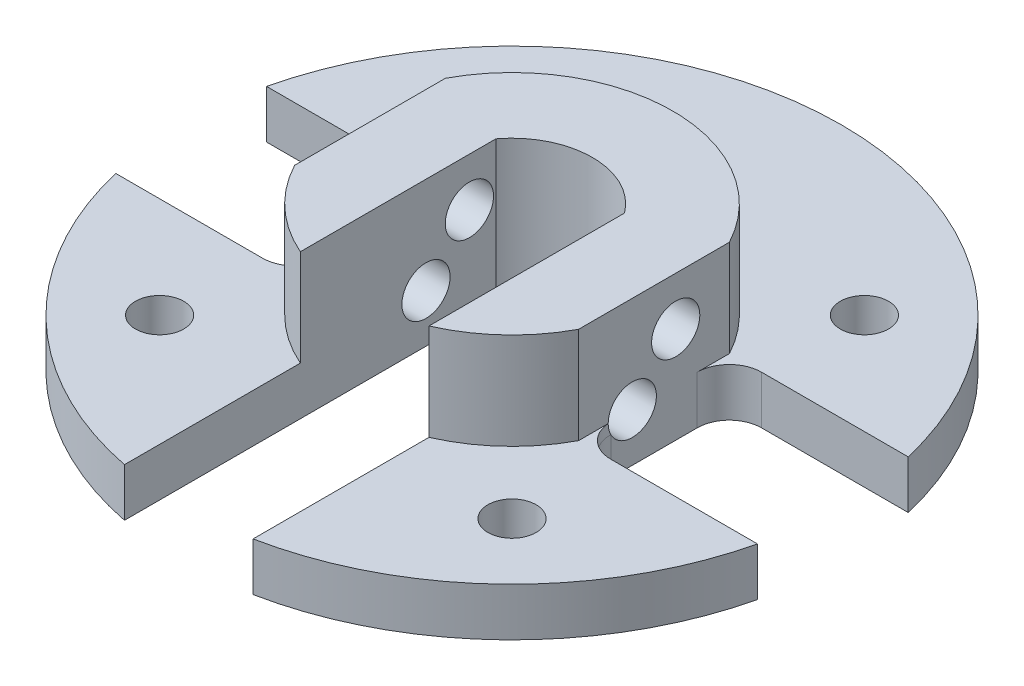
SolidWorks part; units mm, degrees
note: The reader was unsure of these and kept them because the rebuilt part matched: shared geometry of "Sketch1<3>".
ref_plane "Front Plane" through (0, 0, 0) normal (0, 0, 1) x (1, 0, 0)
ref_plane "Top Plane" through (0, 0, 0) normal (0, 1, 0) x (1, 0, 0)
ref_plane "Right Plane" through (0, 0, 0) normal (1, 0, 0) x (0, 0, -1)
sketch "Sketch1" plane through (0, 0, 0) normal (0, 1, 0) x (1, 0, 0)
  line L0 (0, 0) -> (14.2015, 0) construction
  line L1 (0, 0) -> (10.9602, 10.9602) construction
  line L2 (-4, -20.106) -> (-4, 3)
  line L4 (4, 3) -> (4, -20.106)
  circle A0 centre (0, 0) radius 20.5
  circle A2 centre (10.9602, 10.9602) radius 1.5
  circle A3 centre (10.9602, -10.9602) radius 1.5
  circle A4 centre (-10.9602, -10.9602) radius 1.5
  circle A5 centre (-10.9602, 10.9602) radius 1.5
  arc A6 (4, -9.1652) -> (-4, -9.1652) centre (0, 0) ccw
  arc A7 (-4, 3) -> (4, 3) centre (0, 0) cw
  point P15 (0, 0)
  point P18 (0, 0)
  point P21 (0, 0)
  point P22 (0, 0)
  point P23 (0, 3.326)
  point P24 (0, 0)
  dimension "D1" = 3
  dimension "D4" = 41
  dimension "D8" = 10
  dimension "D7" = 5
  dimension "D2" = 15.5
  dimension "D3" = 45
  dimension "D6" = 8
  dimension "D5" = 4
extrude "Boss-Extrude1" add sketch "Sketch1" against normal blind 3 contours A6 L4 A0 L2 A5 A4 A3 A2 | L2 A7 L4 A6
extrude "Boss-Extrude2" add sketch "Sketch1<3>" along normal blind 6 contours L2 A7 L4 A6
sketch "Sketch1<3>" plane through (0, 0, 0) normal (0, 1, 0) x (1, 0, 0) same geometry as "Sketch1"
sketch "Sketch2" plane through (0, 0, 0) normal (1, 0, 0) x (0, 0, -1)
  line L2 (0, 0) -> (0, 7.084) construction
  line L3 (3, -3) -> (3, 6) construction
  line L4 (-3, -2.75) -> (3, -2.75) construction
  line L5 (-3, -2.75) -> (-3, 5.75) construction
  line L6 (-3, 5.75) -> (3, 5.75) construction
  line L7 (3, -2.75) -> (3, 5.75) construction
  line L8 (-3, -2.75) -> (3, 5.75) construction
  line L9 (-3, 5.75) -> (3, -2.75) construction
  line L10 (3, -3) -> (3, 6)
  line L11 (-20.106, -3) -> (3, -3) construction
  line L12 (-20.106, -3) -> (3, -3)
  line L13 (-9.1652, 6) -> (3, 6) construction
  line L14 (-9.1652, 6) -> (3, 6)
  line L15 (1.35, 3) -> (-1.35, 3) construction
  circle A0 centre (1.35, 3) radius 1.5
  circle A1 centre (-1.35, 0) radius 1.5
  circle A2 centre (-1.35, 0) radius 3 construction
  circle A3 centre (1.35, 3) radius 3 construction
  point P2 (0, 1.5)
  point P9 (0, 3)
  point P18 (0, 0)
  point P19 (0, 0)
  point P20 (0, 0)
  point P22 (1.7256, 3)
  point P23 (0, 0)
  dimension "D2" = 3
  dimension "D4" = 6
  dimension "D5" = 6
  dimension "D1" = 8.5
  dimension "D3" = 0.25
  dimension "D6" = 2.7
extrude "Cut-Extrude2" cut sketch "Sketch2" against normal through all both and the other way through all contours A1 | A0
sketch "Sketch3" plane through (0, 6, 0) normal (0, 1, 0) x (1, 0, 0)
  line L0 (-8.8324, -4.6891) -> (-8.8324, 4.6891)
  line L1 (8.8324, -4.6891) -> (8.8324, 4.6891)
  line L2 (-8.8324, -4.6891) -> (-19.9565, -4.6891)
  line L3 (-8.8324, 4.6891) -> (-19.9565, 4.6891)
  line L4 (8.8324, 4.6891) -> (19.9565, 4.6891)
  line L5 (8.8324, -4.6891) -> (19.9565, -4.6891)
  arc A0 (4, -9.1652) -> (-4, -9.1652) centre (0, 0) ccw construction
  arc A1 (4, -9.1652) -> (-4, -9.1652) centre (0, 0) ccw
  arc A2 (4, -20.106) -> (-4, -20.106) centre (0, 0) ccw construction
  arc A3 (4, -20.106) -> (-4, -20.106) centre (0, 0) ccw
  point P9 (0, 0)
  point P13 (0, 0)
  point P14 (0, 0)
  point P16 (0, 0)
  arc M4 (4, -9.1652) -> (-4, -9.1652) centre (0, 0) ccw
extrude "Cut-Extrude3" cut sketch "Sketch3" against normal through all both and the other way through all contours L3 A3 L2 M4 | L0 M4 | L1 M4 | L5 A3 L4 M4
fillet "Fillet1" radius 2 4 edges at (8.8324, -1.5, 4.6891) (8.8324, -1.5, -4.6891) (-8.8324, -1.5, 4.6891) (-8.8324, -1.5, -4.6891)
